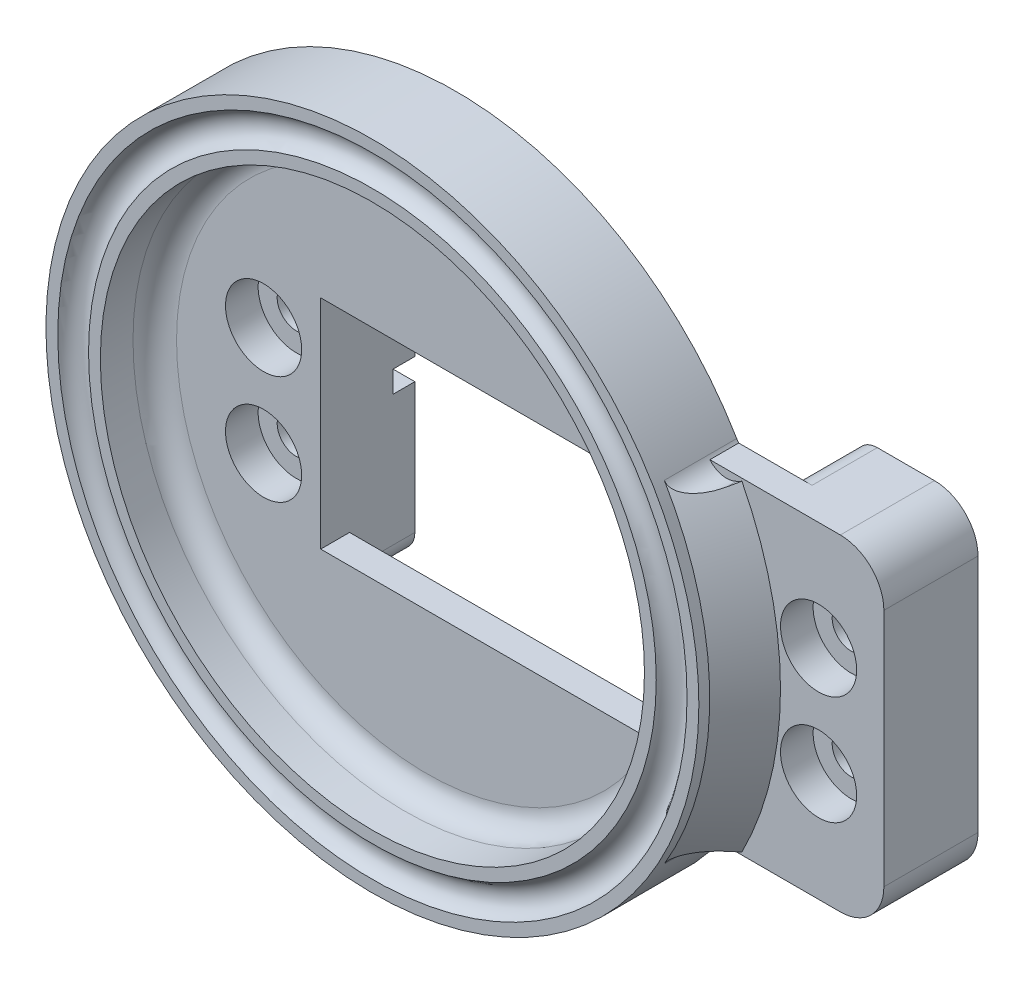
SolidWorks part; units mm, degrees
ref_plane "Спереди" through (0, 0, 0) normal (0, 0, 1) x (1, 0, 0)
ref_plane "Сверху" through (0, 0, 0) normal (0, 1, 0) x (1, 0, 0)
ref_plane "Справа" through (0, 0, 0) normal (1, 0, 0) x (0, 0, -1)
sketch "Эскиз1" plane through (0, 0, 0) normal (0, 0, 1) x (1, 0, 0)
  circle A0 centre (0, 0) radius 25
  circle A1 centre (0, 0) radius 30
  circle A2 centre (0, 0) radius 27.5 construction
  dimension "D1" = 50
  dimension "D2" = 60
  dimension "D3" = 55
extrude "Бобышка-Кольцо" add sketch "Эскиз1" along normal blind 5
sketch "Эскиз2" plane through (0, 0, 0) normal (0, 1, 0) x (1, 0, 0)
  line L0 (-30, -5) -> (30, -5) construction
  line L1 (-30, -5) -> (30, -5)
  line L2 (0, -25.9268) -> (0, 0) construction
  circle A0 centre (-27.5, -5.5) radius 1.5
  dimension "D1" = 3
  dimension "D2" = 27.5
  dimension "D3" = 0.5
revolve "Вырез-Канавка" cut sketch "Эскиз2" angle 360 about L2 region at (-27.5, 0, 4.5858) region at (-27.5, 0, 5.8767)
sketch "Эскиз3" plane through (0, 0, 0) normal (0, 0, -1) x (-1, 0, 0)
  line L0 (-30, 0) -> (30, 0) construction
  line L1 (-10.5, 10) -> (-10.5, -10) construction
  line L2 (9.75, 10) -> (-30.75, 10)
  line L3 (9.75, 10) -> (9.75, -10)
  line L4 (9.75, -10) -> (-30.75, -10)
  line L5 (-30.75, 10) -> (-30.75, -10)
  line L6 (-1, -15) -> (-1, 15)
  line L7 (-42, -15) -> (-20, -15)
  line L8 (-42, -15) -> (-42, 15)
  line L9 (-42, 15) -> (-20, 15)
  line L10 (-20, -15) -> (-20, 15)
  line L11 (21, 15) -> (-1, 15)
  line L12 (21, -15) -> (-1, -15)
  line L13 (21, -15) -> (21, 15)
  circle A0 centre (0, 0) radius 5
  circle A1 centre (0, 0) radius 30 construction
  circle A2 centre (0, 0) radius 25 construction
  circle A3 centre (0, 0) radius 25
  circle A4 centre (15, 5) radius 1.75
  circle A5 centre (0, 0) radius 30
  circle A6 centre (0, 0) radius 30
  circle A7 centre (15, -5) radius 1.75
  circle A8 centre (-36, 5) radius 1.75
  circle A9 centre (-36, -5) radius 1.75
  circle M12 centre (0, 0) radius 30
  circle M13 centre (0, 0) radius 25
  dimension "D2" = 10
  dimension "D8" = 3.5
  dimension "D3" = 20
  dimension "D4" = 9.75
  dimension "D5" = 40.5
  dimension "D6" = 10
  dimension "D7" = 15
  dimension "D9" = 30
  dimension "D10" = 12
  dimension "D1" = 0
extrude "Бобышка-Основание сервы" add sketch "Эскиз3" along normal blind 2.65 contours L10 L2 L3 L4 A7 A4 M13 | L9 L8 L7 L4 L5 L2 A8 A9 M12 | L7 L4 M12 M13 | L9 L2 M12 M13 | L10 L4 M13 | L2 L10 M13 | L9 L7 M12 M13 | L11 L10 L2 L6 M13 | L12 L6 L4 L10 M13 | L13 M13 | L13 L11 M13 | L12 L13 M13 region at (-12.588, 0, 0) region at (2.6631, 17.4093, 0) region at (21.0154, 11.7376, 0) region at (2.6631, -17.4093, 0) region at (24.3825, 12.5446, 0) region at (21.0154, -11.7376, 0) region at (22.9904, 15.8206, 0) region at (-20.6708, 14.5276, 0) region at (35.6526, 0, 0) region at (24.3825, -12.5446, 0) region at (-22.6115, 0, 0) region at (-20.6708, -14.5276, 0)
sketch "Эскиз4" plane through (0, 0, -2.65) normal (0, 0, -1) x (-1, 0, 0)
  line L4 (-42, -15) -> (-20, -15)
  line L5 (-20, -15) -> (-20, 15)
  line L6 (-20, 15) -> (-42, 15)
  line L7 (-42, 15) -> (-42, -15)
  line L8 (-42, -15) -> (-20, -15)
  line L9 (-20, -15) -> (-20, 15)
  line L10 (-20, 15) -> (-42, 15)
  line L11 (-42, 15) -> (-42, -15)
  line L12 (9.75, 10) -> (-30.75, 10)
  line L13 (9.75, -10) -> (9.75, 10)
  line L14 (-30.75, -10) -> (9.75, -10)
  line L15 (-30.75, 10) -> (-30.75, -10)
  line L16 (9.75, 10) -> (-30.75, 10)
  line L17 (9.75, -15) -> (9.75, 15)
  line L18 (-30.75, -10) -> (9.75, -10)
  line L19 (-30.75, 15) -> (-30.75, -15)
  line L20 (21, 15) -> (-1, 15)
  line L21 (21, -15) -> (21, 15)
  line L22 (-1, -15) -> (21, -15)
  line L23 (-1, 15) -> (-1, -15)
  line L24 (21, 15) -> (-1, 15)
  line L25 (21, -15) -> (21, 15)
  line L26 (-1, -15) -> (21, -15)
  line L27 (-1, 15) -> (-1, -15)
  circle A5 centre (0, 0) radius 5
  circle A6 centre (0, 0) radius 5
  circle A7 centre (-36, -5) radius 1.75
  circle A8 centre (-36, -5) radius 1.75
  circle A9 centre (-36, 5) radius 1.75
  circle A10 centre (-36, 5) radius 1.75
  circle A11 centre (15, -5) radius 1.75
  circle A12 centre (15, -5) radius 1.75
  circle A13 centre (15, 5) radius 1.75
  circle A14 centre (15, 5) radius 1.75
  line M20 (-30.75, -10) -> (-30.75, 10)
  line M22 (9.75, 10) -> (9.75, -10)
  line M26 (-42, 15) -> (-42, -15)
  line M27 (-42, -15) -> (-25.9808, -15)
  circle M28 centre (15, -5) radius 1.75
  circle M29 centre (15, 5) radius 1.75
  circle M30 centre (-36, 5) radius 1.75
  circle M31 centre (-36, -5) radius 1.75
  dimension "D3" = 0
  dimension "D4" = 0
  dimension "D5" = 0
  dimension "D6" = 0
  dimension "D7" = 0
  dimension "D8" = 0
  dimension "D9" = 0
  dimension "D10" = 0
extrude "Бобышка-Вытянуть3" add sketch "Эскиз4" along normal blind 6 contours L17 L26 L25 L24 M22 M28 M29 | L19 L10 M26 M27 M20 M31 M30 region at (36.3977, 0, -2.65) region at (-15.3977, 0, -2.65)
sketch "Эскиз5" plane through (0, 0, 0) normal (0, 1, 0) x (1, 0, 0)
  line L0 (30.75, 8.65) -> (30.75, 2.65) construction
  line L1 (30.75, 8.65) -> (30.75, 2.65)
  line L2 (-9.75, 8.65) -> (-9.75, 2.65) construction
  line L3 (-9.75, 8.65) -> (-9.75, 2.65)
  line L4 (-9.75, 8.65) -> (-17.25, 8.65)
  line L5 (-17.25, 8.65) -> (-9.75, 6.65)
  line L6 (30.75, 8.65) -> (38.25, 8.65)
  line L7 (38.25, 8.65) -> (30.75, 6.65)
  dimension "D1" = 7.5
  dimension "D2" = 2
  dimension "D3" = 7.5
  dimension "D4" = 2
extrude "Вырез-уголочки серв" cut sketch "Эскиз5" against normal mid plane 2 contours L7 L6 L1 | L4 L5 L3 region at (33.25, 0, -7.9833) region at (-12.25, 0, -7.9833)
sketch "Эскиз6" plane through (0, 0, 0) normal (0, 0, 1) x (1, 0, 0)
  line L1 (-13.2679, 8) -> (-16.7321, 8)
  line L2 (-16.7321, 8) -> (-18.4641, 5)
  line L3 (-18.4641, 5) -> (-16.7321, 2)
  line L4 (-16.7321, 2) -> (-13.2679, 2)
  line L5 (-13.2679, 2) -> (-11.5359, 5)
  line L6 (-11.5359, 5) -> (-13.2679, 8)
  line L7 (-16.7321, -2) -> (-18.4641, -5)
  line L8 (-18.4641, -5) -> (-16.7321, -8)
  line L9 (-16.7321, -8) -> (-13.2679, -8)
  line L10 (-13.2679, -8) -> (-11.5359, -5)
  line L11 (-11.5359, -5) -> (-13.2679, -2)
  line L12 (-13.2679, -2) -> (-16.7321, -2)
  line L13 (34.2679, 8) -> (32.5359, 5)
  line L14 (32.5359, 5) -> (34.2679, 2)
  line L15 (34.2679, 2) -> (37.7321, 2)
  line L16 (37.7321, 2) -> (39.4641, 5)
  line L17 (39.4641, 5) -> (37.7321, 8)
  line L18 (37.7321, 8) -> (34.2679, 8)
  line L19 (34.2679, -2) -> (32.5359, -5)
  line L20 (32.5359, -5) -> (34.2679, -8)
  line L21 (34.2679, -8) -> (37.7321, -8)
  line L22 (37.7321, -8) -> (39.4641, -5)
  line L23 (39.4641, -5) -> (37.7321, -2)
  line L24 (37.7321, -2) -> (34.2679, -2)
  circle A0 centre (-15, 5) radius 1.75 construction
  circle A1 centre (-15, 5) radius 1.75
  circle A2 centre (-15, -5) radius 1.75 construction
  circle A3 centre (-15, -5) radius 1.75
  circle A4 centre (36, 5) radius 1.75 construction
  circle A5 centre (36, 5) radius 1.75
  circle A6 centre (36, -5) radius 1.75 construction
  circle A7 centre (36, -5) radius 1.75
  circle A8 centre (-15, 5) radius 3 construction
  circle A9 centre (-15, -5) radius 3 construction
  circle A10 centre (36, 5) radius 3 construction
  circle A11 centre (36, -5) radius 3 construction
  circle A12 centre (-15, 5) radius 3.5
  circle A13 centre (-15, -5) radius 3.5
  circle A14 centre (36, 5) radius 3.5
  circle A15 centre (36, -5) radius 3.5
  dimension "D1" = 6
  dimension "D2" = 6
  dimension "D3" = 6
  dimension "D4" = 6
  dimension "D5" = 7
extrude "Вырез-под гайки" cut sketch "Эскиз6" against normal blind 3 contours A12 L6 L5 L4 L3 L2 L1 | L5 L6 L1 L2 L3 L4 A1 | A13 L12 L11 L10 L9 L8 L7 | L11 L12 L7 L8 L9 L10 A3 | A14 L18 L17 L16 L15 L14 L13 | L17 L18 L13 L14 L15 L16 A5 | A15 L24 L23 L22 L21 L20 L19 | L23 L24 L19 L20 L21 L22 A7 region at (-12.4813, 6.4542, 0) region at (-15, -2.0917, 0) region at (36, 7.9083, 0) region at (36, -2.0917, 0) region at (-18.4901, 5, 0) region at (-18.4901, -5, 0) region at (32.5099, 5, 0) region at (32.5099, -5, 0)
sketch "Эскиз7" plane through (0, 0, 0) normal (0, -1, 0) x (1, 0, 0)
  line L1 (30, 0) -> (32.5, 0)
  line L2 (30, 0) -> (30, 4)
  line L3 (30, 4) -> (32.5, 0)
  line L5 (30, 0) -> (30, 5) construction
  line L6 (30, 0) -> (30, 5)
  line L7 (0, 0) -> (0, 18.0554) construction
  dimension "D1" = 4
  dimension "D2" = 2.5
revolve "Повернуть закрыть дырочку" add sketch "Эскиз7" angle 27 about L7 region at (30.8333, 0, 1.3333) other way angle 27
fillet "Скругление 2мм изнутри" radius 2 1 edges at (-25, 0, 0)
fillet "Скругление 2мм" radius 2 6 edges at (26.7302, 13.6197, 2) (26.7302, -13.6197, 2) (30.75, -15, -5.65) (30.75, 15, -5.65) (-9.75, -15, -5.65) (-9.75, 15, -5.65)
fillet "Скругление 4мм" radius 4 4 edges at (-21, -15, -5.65) (-21, 15, -5.65) (42, 15, -4.325) (42, -15, -4.325)
